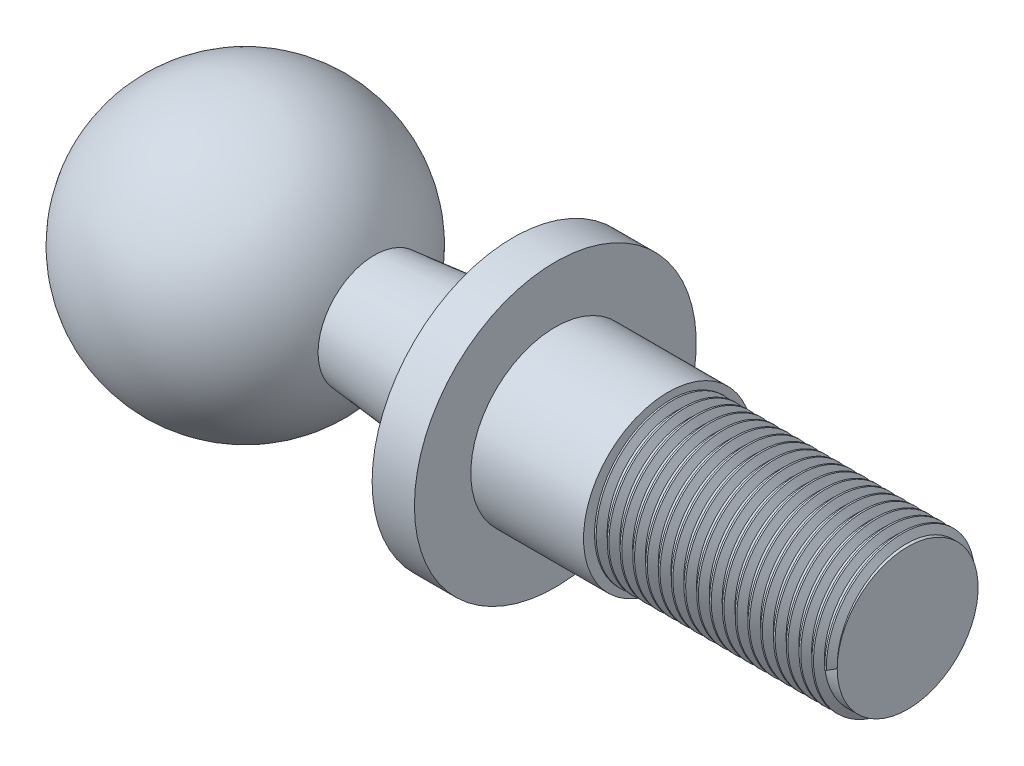
SolidWorks part; units mm, degrees
ref_plane "정면" through (0, 0, 0) normal (0, 0, 1) x (1, 0, 0)
ref_plane "윗면" through (0, 0, 0) normal (0, 1, 0) x (1, 0, 0)
ref_plane "우측면" through (0, 0, 0) normal (1, 0, 0) x (0, 0, -1)
sketch "스케치1" plane through (0, 0, 0) normal (1, 0, 0) x (0, 0, -1)
  circle A0 centre (0, 0) radius 3
  dimension "D1" = 6
extrude "보스-돌출1" add sketch "스케치1" along normal blind 4
sketch "스케치2" plane through (0, 0, 0) normal (-1, 0, 0) x (0, 0, 1)
  circle A0 centre (0, 0) radius 5
  dimension "D1" = 10
extrude "보스-돌출2" add sketch "스케치2" along normal blind 1.5
sketch "스케치3" plane through (0, 0, 0) normal (0, 0, 1) x (1, 0, 0)
  line L0 (-6, 0) -> (-16, 0)
  line L1 (-11, 0) -> (-21.7004, 0) construction
  arc A0 (-6, 0) -> (-16, 0) centre (-11, 0) ccw
  dimension "D2" = 10
  dimension "D1" = 11
revolve "회전1" add sketch "스케치3" angle 360 about L1
sketch "스케치4" plane through (0, 0, 0) normal (0, 0, 1) x (1, 0, 0)
  line L0 (0, 0) -> (-19.1147, 0) construction
  line L1 (-16.757, 2) -> (-5.0996, 2) construction
  line L2 (-17.6879, -2) -> (-5.9394, -2) construction
  line L3 (-15.5826, 2) -> (-15.5826, -2)
  line L4 (-15.5826, -2) -> (-16.3495, -3.1954)
  line L5 (-16.3495, -3.1954) -> (-16.5376, 3.6662)
  line L6 (-16.5376, 3.6662) -> (-15.5826, 2)
  line L7 (-11, 0) -> (-11, 7.5992) construction
  line L8 (-5.6505, -3.1954) -> (-5.4624, 3.6662)
  line L9 (-6.4174, -2) -> (-5.6505, -3.1954)
  line L10 (-6.4174, 2) -> (-6.4174, -2)
  line L11 (-5.4624, 3.6662) -> (-6.4174, 2)
  circle A0 centre (-11, 0) radius 5 construction
  point P7 (-15.5826, 2)
  point P13 (-15.5826, -2)
  dimension "D1" = 2
  dimension "D2" = 2
extrude "컷-돌출1" cut sketch "스케치4" against normal through all both and the other way through all
sketch "스케치5" plane through (-6.4174, 0, 0) normal (1, 0, 0) x (0, 0, -1)
  circle A0 centre (0, 0) radius 2 construction
  circle A1 centre (0, 0) radius 2
sketch "스케치6" plane through (-1.5, 0, 0) normal (-1, 0, 0) x (0, 0, 1)
  circle A0 centre (0, 0) radius 2.5
  dimension "D1" = 5
loft "로프트1" add profiles "스케치6", "스케치5" connector at (-1.5, 0.1821, -2.4934) connector at (-6.4174, -0.0775, -1.9985)
sketch "스케치12" plane through (4, 0, 0) normal (1, 0, 0) x (0, 0, -1)
  circle A0 centre (0, 0) radius 2.5
  dimension "D1" = 5
extrude "보스-돌출3" add sketch "스케치12" along normal blind 8.5 contours A0
thread "나사산1" pitch 0.4536 method extrude trim with end face yes profile "나사산 프로파일3" start angle 0, offset 0, length 8.5, pitch 0.4536, diameter 5
ref_plane "평면3" through (12.5, 0, 2.5) normal (0, -1, 0) x (0, 0, 1)
sketch "나사산 프로파일3" plane through (12.5, 0, 2.5) normal (0, -1, 0) x (0, 0, 1)
  line L0 (0, 0) -> (0, 0.4536) construction
  line L1 (0, 0) -> (0.2455, 0.1417)
  line L2 (0.2455, 0.1417) -> (0.2455, 0.1984)
  line L3 (0.2455, 0.1984) -> (0, 0.3402)
  line L4 (0.2455, 0.1701) -> (0, 0.1701) construction
  line L11 (0, 0) -> (0, 0.3402)
  point P2 (0, 0)
  dimension "Pitch" = 0.4536
  dimension "Profile_Angle" = 60
  dimension "Profile_Land" = 0.0567
  dimension "Profile_Height" = 0.2455
